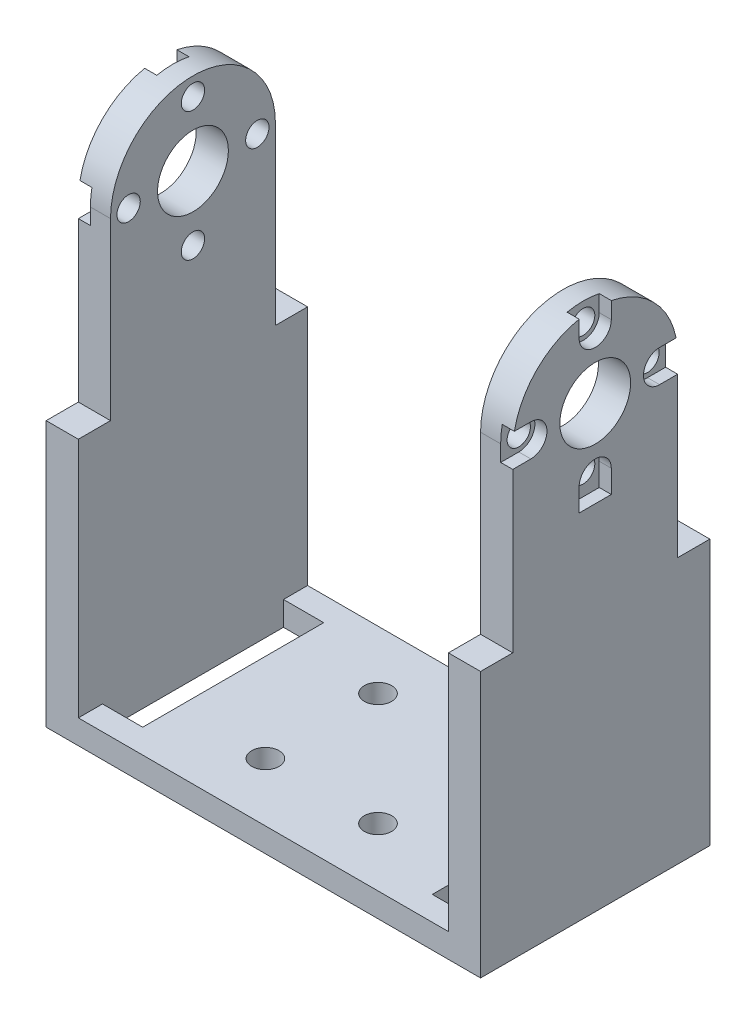
SolidWorks part; units mm, degrees
ref_plane "Front Plane" through (0, 0, 0) normal (0, 0, 1) x (1, 0, 0)
ref_plane "Top Plane" through (0, 0, 0) normal (0, 1, 0) x (1, 0, 0)
ref_plane "Right Plane" through (0, 0, 0) normal (1, 0, 0) x (0, 0, -1)
sketch "Sketch1" plane through (0, 0, 0) normal (0, 1, 0) x (1, 0, 0)
  line L0 (0, 0) -> (0, -7.6155) construction
  line L1 (-18, 14.25) -> (18, 14.25)
  line L2 (-18, 14.25) -> (-18, -14.25)
  line L3 (-18, -14.25) -> (18, -14.25)
  line L4 (18, 14.25) -> (18, -14.25)
  line L5 (0, 0) -> (0, 12.9892) construction
  line L6 (-18, 14.25) -> (-27, 14.25)
  line L7 (-18, 14.25) -> (-18, -14.25)
  line L8 (-18, -14.25) -> (-27, -14.25)
  line L9 (-27, 14.25) -> (-27, -14.25)
  line L10 (18, 14.25) -> (27, 14.25)
  line L11 (18, 14.25) -> (18, -14.25)
  line L12 (18, -14.25) -> (27, -14.25)
  line L13 (27, 14.25) -> (27, -14.25)
  line L14 (-23, 11.25) -> (-18, 11.25)
  line L15 (-23, 11.25) -> (-23, -11.25)
  line L16 (-23, -11.25) -> (-18, -11.25)
  line L17 (-18, 11.25) -> (-18, -11.25)
  line L18 (18, 11.25) -> (18, -11.25)
  line L19 (23, -11.25) -> (18, -11.25)
  line L20 (23, 11.25) -> (23, -11.25)
  line L21 (23, 11.25) -> (18, 11.25)
  circle A0 centre (0, 0) radius 7.5
  circle A1 centre (-9, 8.25) radius 1.7
  circle A2 centre (-9, -8.25) radius 1.7
  circle A3 centre (9, -8.25) radius 1.7
  circle A4 centre (9, 8.25) radius 1.7
  point P0 (0, 0)
  dimension "D3" = 9
  dimension "D4" = 8.25
  dimension "D5" = 8.25
  dimension "D6" = 9
  dimension "D7" = 9
  dimension "D9" = 15
  dimension "D14" = 3.4
  dimension "D1" = 36
  dimension "D2" = 28.5
  dimension "D8" = 9
  dimension "D10" = 4
  dimension "D11" = 3
  dimension "D12" = 3
  dimension "D13" = 5
extrude "Boss-Extrude2" add sketch "Sketch1" along normal blind 3 contours L6 L9 L8 L2 | L13 L10 L4 L12 | L4 L1 L2 L3 A3 A2 A1 A0 A4 region at (0, 0, -13.7908) region at (-24.0625, 0, 0) region at (24.0625, 0, 0)
sketch "Sketch2" plane through (0, 3, 0) normal (0, 1, 0) x (1, 0, 0)
  line L5 (27, 14.25) -> (27, -14.25) construction
  line L6 (27, 10.25) -> (23, 10.25)
  line L7 (27, 10.25) -> (27, -10.25)
  line L8 (27, -10.25) -> (23, -10.25)
  line L9 (23, 10.25) -> (23, -10.25)
  line L10 (27, 14.25) -> (-27, 14.25) construction
  dimension "D1" = 4
  dimension "D2" = 20.5
  dimension "D3" = 4
extrude "Boss-Extrude3" add sketch "Sketch2" along normal blind 21.75
sketch "Sketch4" plane through (27, 0, 0) normal (1, 0, 0) x (0, 0, -1)
  line L0 (-10.25, 24.75) -> (10.25, 24.75) construction
  circle A0 centre (0, 24.75) radius 10.25
  point P18 (0, 17.75)
  line M5 (10.25, 24.75) -> (-10.25, 24.75)
extrude "Boss-Extrude4" add sketch "Sketch4" against normal blind 4 contours A0 M5 | M5 | M5 | A0 M5 region at (27, 29.1002, 0) region at (27, 20.3998, 0)
ref_plane "Plane1" through (0, 0, 0) normal (1, 0, 0) x (0, 0, -1)
mirror "Mirror1" about plane through (0, 0, 0) normal (1, 0, 0) of "Boss-Extrude3", "Boss-Extrude4"
sketch "Sketch6" plane through (27, 0, 0) normal (1, 0, 0) x (0, 0, -1)
  line L0 (-10.25, 24.75) -> (10.25, 24.75) construction
  line L1 (0, 35) -> (0, 14.5) construction
  circle A6 centre (0, 24.75) radius 4.4
  circle A7 centre (0, 24.75) radius 8
  circle A8 centre (0, 32.75) radius 1.45
  circle A9 centre (8, 24.75) radius 1.45
  circle A10 centre (0, 16.75) radius 1.45
  circle A11 centre (-8, 24.75) radius 1.45
  circle A12 centre (0, 24.75) radius 10.25
  point P21 (0, 24.75)
  dimension "D1" = 8.8
  dimension "D2" = 16
  dimension "D3" = 4
  dimension "D4" = 2.9
extrude "Cut-Extrude3" cut sketch "Sketch6" against normal blind 4 contours A6 | A7 A11 | A7 A11 | A7 A10 | A7 A10 | A7 A9 | A7 A9 | A7 A8 | A7 A8 region at (27, 24.75, 0) region at (27, 24.75, -7.3615) region at (27, 24.75, -8.5911) region at (27, 32.1115, 0) region at (27, 33.3411, 0) region at (27, 16.1589, 0) region at (27, 17.3885, 0) region at (27, 24.75, 7.3615) region at (27, 24.75, 8.5911)
mirror "Mirror3" about plane through (0, 0, 0) normal (1, 0, 0) of "Cut-Extrude3"
sketch "Sketch7" plane through (27, 0, 0) normal (1, 0, 0) x (0, 0, -1)
  line L0 (10.8224, 26.75) -> (10.8224, 22.75)
  line L2 (-2, 32.75) -> (-2, 35.5724)
  line L3 (-2, 35.5724) -> (2, 35.5724)
  line L4 (2, 32.75) -> (2, 35.5724)
  line L5 (8, 22.75) -> (10.8224, 22.75)
  line L6 (8, 26.75) -> (10.8224, 26.75)
  line L7 (2, 13.9276) -> (-2, 13.9276)
  line L8 (-2, 16.75) -> (-2, 13.9276)
  line L9 (2, 16.75) -> (2, 13.9276)
  line L10 (-10.8224, 22.75) -> (-10.8224, 26.75)
  line L11 (-8, 26.75) -> (-10.8224, 26.75)
  line L12 (-8, 22.75) -> (-10.8224, 22.75)
  circle A0 centre (0, 32.75) radius 2
  circle A1 centre (0, 24.75) radius 8
  circle A2 centre (8, 24.75) radius 2
  circle A3 centre (0, 16.75) radius 2
  circle A4 centre (-8, 24.75) radius 2
  point P15 (0, 24.75)
  point P32 (0, 24.75)
  circle M1 centre (-8, 24.75) radius 1.45
  circle M2 centre (0, 16.75) radius 1.45
  circle M3 centre (8, 24.75) radius 1.45
  circle M4 centre (0, 32.75) radius 1.45
  line M6 (10.25, 3) -> (10.25, 24.75)
  arc M7 (10.25, 24.75) -> (-10.25, 24.75) centre (0, 24.75) ccw
  line M8 (-10.25, 24.75) -> (-10.25, 3)
  dimension "D1" = 4
  dimension "D3" = 4
  dimension "D2" = 4
  dimension "D4" = 4
extrude "Cut-Extrude4" cut sketch "Sketch7" against normal blind 1.5 contours A1 M1 | A1 M1 | A1 A0 M4 | A0 A1 M4 | A1 A2 M3 | A1 A2 M3 | A1 A3 M2 | A1 A3 M2 | L4 L3 L2 M7 | A0 L4 L2 M7 | A2 L5 L6 M6 M7 | A3 L8 L7 L9 | A4 L11 L12 M7 M8 | A4 region at (27, 25.7503, -10.155) region at (27, 26.1318, -9.3818) region at (27, 35.2508, 0) region at (27, 33.7765, -1.9541) region at (27, 26.4558, -7.7711) region at (27, 32.6276, -1.9503) region at (27, 30.7939, 0) region at (27, 26.7041, 9.0265) region at (27, 16.8724, -1.9503) region at (27, 16.9789, -1.7058) region at (27, 14.633, 0) region at (27, 24.75, 7.3615) region at (27, 24.75, 8.5911)
mirror "Mirror4" about plane through (0, 0, 0) normal (1, 0, 0) of "Cut-Extrude4"
sketch "Sketch8" plane through (0, 3, 0) normal (0, 1, 0) x (1, 0, 0)
  line L0 (27, -14.25) -> (-27, -14.25) construction
  line L1 (-14.3907, 14.25) -> (14.3907, 14.25)
  line L2 (-14.3907, 14.25) -> (-14.3907, -14.25)
  line L3 (-14.3907, -14.25) -> (14.3907, -14.25)
  line L4 (14.3907, 14.25) -> (14.3907, -14.25)
  line L5 (-14.3907, 14.25) -> (14.3907, -14.25) construction
  line L6 (-14.3907, -14.25) -> (14.3907, 14.25) construction
  point P0 (0, 0)
extrude "Boss-Extrude5" add sketch "Sketch8" against normal blind 3
sketch "Sketch9" plane through (0, 3, 0) normal (0, 1, 0) x (1, 0, 0)
  line L3 (-7, 7) -> (7, 7)
  line L4 (-7, 7) -> (-7, -7)
  line L5 (-7, -7) -> (7, -7)
  line L6 (7, 7) -> (7, -7)
  line L7 (-7, 7) -> (7, -7) construction
  line L8 (-7, -7) -> (7, 7) construction
  circle A0 centre (0, 0) radius 5
  circle A2 centre (-7, 7) radius 1.7
  circle A3 centre (7, 7) radius 1.7
  circle A4 centre (7, -7) radius 1.7
  circle A5 centre (-7, -7) radius 1.7
  dimension "D1" = 14
  dimension "D2" = 14
  dimension "D3" = 10
  dimension "D4" = 3.4
  dimension "D5" = 2
  dimension "D6" = 2
extrude "Cut-Extrude5" cut sketch "Sketch9" against normal blind 3 contours L4 A5 L5 | L5 A4 L6 | L6 A3 L3 | L3 A3 L6 | L5 A5 L4 | L6 A4 L5 | A2 region at (7.2405, 3, -7.2405) region at (6.2785, 3, -6.2785) region at (-6.2785, 3, 6.2785) region at (-7.2405, 3, 7.2405) region at (7.2405, 3, 7.2405) region at (6.2785, 3, 6.2785)
sketch "Sketch10" plane through (0, 0, 0) normal (0, -1, 0) x (1, 0, 0)
  line L1 (-27, 14.25) -> (27, 14.25)
  line L2 (-27, 14.25) -> (-27, -14.25)
  line L3 (-27, -14.25) -> (27, -14.25)
  line L4 (27, 14.25) -> (27, -14.25)
  line L5 (-23, 11.25) -> (-18, 11.25)
  line L6 (-23, 11.25) -> (-23, -11.25)
  line L7 (-23, -11.25) -> (-18, -11.25)
  line L8 (-18, 11.25) -> (-18, -11.25)
  line L9 (18, -11.25) -> (23, -11.25)
  line L10 (18, -11.25) -> (18, 11.25)
  line L11 (18, 11.25) -> (23, 11.25)
  line L12 (23, -11.25) -> (23, 11.25)
  circle A0 centre (-7, 7) radius 1.7
  circle A1 centre (7, 7) radius 1.7
  circle A2 centre (7, -7) radius 1.7
  circle A3 centre (-7, -7) radius 1.7
extrude "Boss-Extrude7" add sketch "Sketch10" along normal blind 30
sketch "Sketch11" plane through (0, 0, 14.25) normal (0, 0, 1) x (1, 0, 0)
  line L0 (27, -30) -> (-27, -30) construction
  line L1 (-23, 3) -> (23, 3)
  line L2 (-23, 3) -> (-23, -27)
  line L3 (-23, -27) -> (23, -27)
  line L4 (23, 3) -> (23, -27)
  dimension "D1" = 3
extrude "Cut-Extrude6" cut sketch "Sketch11" against normal blind 30
